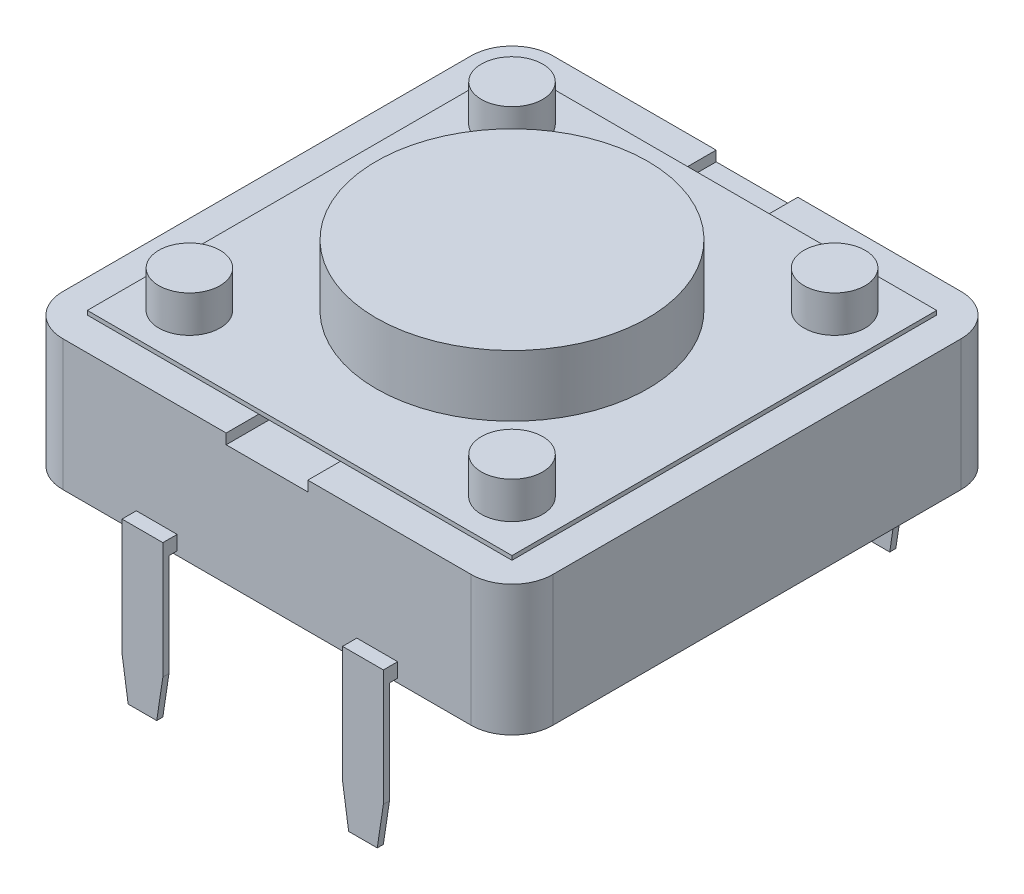
SolidWorks part; units mm, degrees
ref_plane "Front Plane" through (0, 0, 0) normal (0, 0, 1) x (1, 0, 0)
ref_plane "Top Plane" through (0, 0, 0) normal (0, 1, 0) x (1, 0, 0)
ref_plane "Right Plane" through (0, 0, 0) normal (1, 0, 0) x (0, 0, -1)
sketch "Sketch1" plane through (0, 0, 0) normal (0, 1, 0) x (1, 0, 0)
  line L1 (0, 0) -> (12, 0)
  line L2 (0, 0) -> (0, 12)
  line L3 (0, 12) -> (12, 12)
  line L4 (12, 0) -> (12, 12)
  dimension "D1" = 12
  dimension "D2" = 12
extrude "Boss-Extrude1" add sketch "Sketch1" along normal blind 3.2
sketch "Sketch2" plane through (0, 3.2, 0) normal (0, 1, 0) x (1, 0, 0)
  line L0 (12, 12) -> (0, 12) construction
  line L2 (0, 12) -> (0, 0) construction
  line L3 (6, 12) -> (6, 0) construction
  line L4 (0, 0) -> (12, 0) construction
  line L5 (0, 6) -> (12, 6) construction
  line L6 (12, 0) -> (12, 12) construction
  circle A0 centre (2.05, 9.95) radius 0.75
  circle A1 centre (9.95, 9.95) radius 0.75
  circle A2 centre (2.05, 2.05) radius 0.75
  circle A3 centre (9.95, 2.05) radius 0.75
  dimension "D1" = 1.5
  dimension "D2" = 2.05
  dimension "D3" = 2.05
extrude "Boss-Extrude2" add sketch "Sketch2" along normal blind 1
sketch "Sketch3" plane through (0, 3.2, 0) normal (0, 1, 0) x (1, 0, 0)
  line L9 (0.8, 11.2) -> (0.8, 0.8)
  line L10 (0.8, 0.8) -> (11.2, 0.8)
  line L11 (11.2, 0.8) -> (11.2, 11.2)
  line L12 (11.2, 11.2) -> (0.8, 11.2)
  line L13 (0.8, 11.2) -> (0.8, 0.8)
  line L14 (0.8, 0.8) -> (11.2, 0.8)
  line L15 (11.2, 0.8) -> (11.2, 11.2)
  line L16 (11.2, 11.2) -> (0.8, 11.2)
  dimension "D1" = 0.8
extrude "Boss-Extrude3" add sketch "Sketch3" along normal blind 0.1
sketch "Sketch4" plane through (0, 3.3, 0) normal (0, 1, 0) x (1, 0, 0)
  line L0 (6, 6) -> (6, 11.2) construction
  line L1 (11.2, 11.2) -> (0.8, 11.2) construction
  line L2 (6, 6) -> (11.2, 6) construction
  line L3 (11.2, 0.8) -> (11.2, 11.2) construction
  circle A0 centre (6, 6) radius 3.325
  dimension "D1" = 6.65
extrude "Boss-Extrude4" add sketch "Sketch4" along normal blind 1.5
fillet "Fillet1" radius 1 4 edges at (0, 1.6, -12) (0, 1.6, 0) (12, 1.6, 0) (12, 1.6, -12)
sketch "Sketch5" plane through (0, 3.2, 0) normal (0, 1, 0) x (1, 0, 0)
  line L0 (11, 12) -> (1, 12) construction
  line L1 (5, 12) -> (7, 12)
  line L2 (5, 12) -> (5, 0)
  line L3 (5, 0) -> (7, 0)
  line L4 (7, 12) -> (7, 0)
  line L5 (1, 0) -> (11, 0) construction
  point P8 (6, 12)
  point P9 (6, 12)
  dimension "D1" = 2
extrude "Cut-Extrude1" cut sketch "Sketch5" against normal blind 0.25
sketch "Sketch6" plane through (0, 0, 0) normal (0, 0, 1) x (1, 0, 0)
  line L1 (2.8, 0.45) -> (3.8, 0.45)
  line L2 (2.8, 0.45) -> (2.8, 0.1)
  line L3 (2.8, 0.1) -> (3.8, 0.1)
  line L4 (3.8, 0.45) -> (3.8, 0.1)
  line L5 (1, 0) -> (11, 0) construction
  line L6 (0, 0) -> (0, 3.2) construction
  line L7 (6, 0) -> (6, 2.95) construction
  line L8 (5, 2.95) -> (7, 2.95) construction
  line L9 (9.2, 0.45) -> (9.2, 0.1)
  line L10 (9.2, 0.1) -> (8.2, 0.1)
  line L11 (8.2, 0.45) -> (8.2, 0.1)
  line L12 (9.2, 0.45) -> (8.2, 0.45)
  dimension "D1" = 0.35
  dimension "D2" = 1
  dimension "D3" = 0.1
  dimension "D4" = 2.8
extrude "Boss-Extrude5" add sketch "Sketch6" along normal blind 0.35
sketch "Sketch7" plane through (0, 0.1, 0) normal (0, -1, 0) x (1, 0, 0)
  line L0 (3.8, 0.35) -> (3.8, 0) construction
  line L1 (2.8, 0.35) -> (3.8, 0.35)
  line L2 (2.8, 0.35) -> (2.8, 0.2)
  line L3 (2.8, 0.2) -> (3.8, 0.2)
  line L4 (3.8, 0.35) -> (3.8, 0.2)
  line L5 (6, 0) -> (6, -12) construction
  line L6 (1, 0) -> (11, 0) construction
  line L7 (11, -12) -> (1, -12) construction
  line L8 (9.2, 0.35) -> (9.2, 0.2)
  line L9 (9.2, 0.35) -> (8.2, 0.35)
  line L10 (8.2, 0.35) -> (8.2, 0.2)
  line L11 (9.2, 0.2) -> (8.2, 0.2)
  dimension "D1" = 0.15
extrude "Boss-Extrude6" add sketch "Sketch7" along normal blind 3.5
sketch "Sketch8" plane through (0, 0, 0.35) normal (0, 0, 1) x (1, 0, 0)
  line L0 (2.8, -2.4) -> (2.95, -3.4)
  line L1 (2.8, 0.45) -> (2.8, -3.4) construction
  line L2 (3.8, -3.4) -> (2.8, -3.4) construction
  line L3 (3.3, -3.4) -> (3.3, 0.45) construction
  line L4 (3.8, 0.45) -> (2.8, 0.45) construction
  line L5 (3.8, -2.4) -> (3.65, -3.4)
  line L6 (6, 0) -> (6, 2.95) construction
  line L7 (1, 0) -> (11, 0) construction
  line L8 (5, 2.95) -> (7, 2.95) construction
  line L9 (8.2, -2.4) -> (8.35, -3.4)
  line L10 (9.2, -2.4) -> (9.05, -3.4)
  line L11 (3.8, -2.4) -> (3.8, -3.4)
  line L12 (3.8, -3.4) -> (3.65, -3.4)
  line L13 (2.95, -3.4) -> (2.8, -3.4)
  line L14 (2.8, -3.4) -> (2.8, -2.4)
  line L15 (9.2, -3.4) -> (9.2, -2.4)
  line L16 (9.05, -3.4) -> (9.2, -3.4)
  line L17 (9.2, -2.4) -> (9.05, -3.4)
  line L18 (8.2, -2.4) -> (8.35, -3.4)
  line L19 (8.2, -3.4) -> (8.35, -3.4)
  line L20 (8.2, -2.4) -> (8.2, -3.4)
  line M1 (2.8, 0.45) -> (2.8, -3.4)
  line M2 (2.8, -3.4) -> (3.8, -3.4)
  line M3 (3.8, -3.4) -> (3.8, 0.45)
  dimension "D1" = 1
  dimension "D2" = 0.35
extrude "Cut-Extrude4" cut sketch "Sketch8" against normal through all contours L0 M1 M2 | L5 M3 M2 | L9 L20 L19 | L10 L16 L15 region at (3.75, -3.0667, 0.35) region at (2.85, -3.0667, 0.35) region at (8.25, -3.0667, 0.35) region at (9.15, -3.0667, 0.35)
ref_plane "Plane1" through (0, 0, -6) normal (0, 0, 1) x (1, 0, 0)
mirror "Mirror1" about plane through (0, 0, -6) normal (0, 0, 1) of "Boss-Extrude6", "Cut-Extrude4", "Boss-Extrude5"
ref_plane "Plane2" through (0, 0, 0.275) normal (0, 0, 1) x (1, 0, 0)
ref_plane "Plane3" through (3.3, 0, 0) normal (1, 0, 0) x (0, 0, -1)
ref_axis "Axis1" through (3.3, 0.2686, 0.275) along (0, -1, 0)
equation "\"D3@Sketch2\"=\"D2@Sketch2\""
